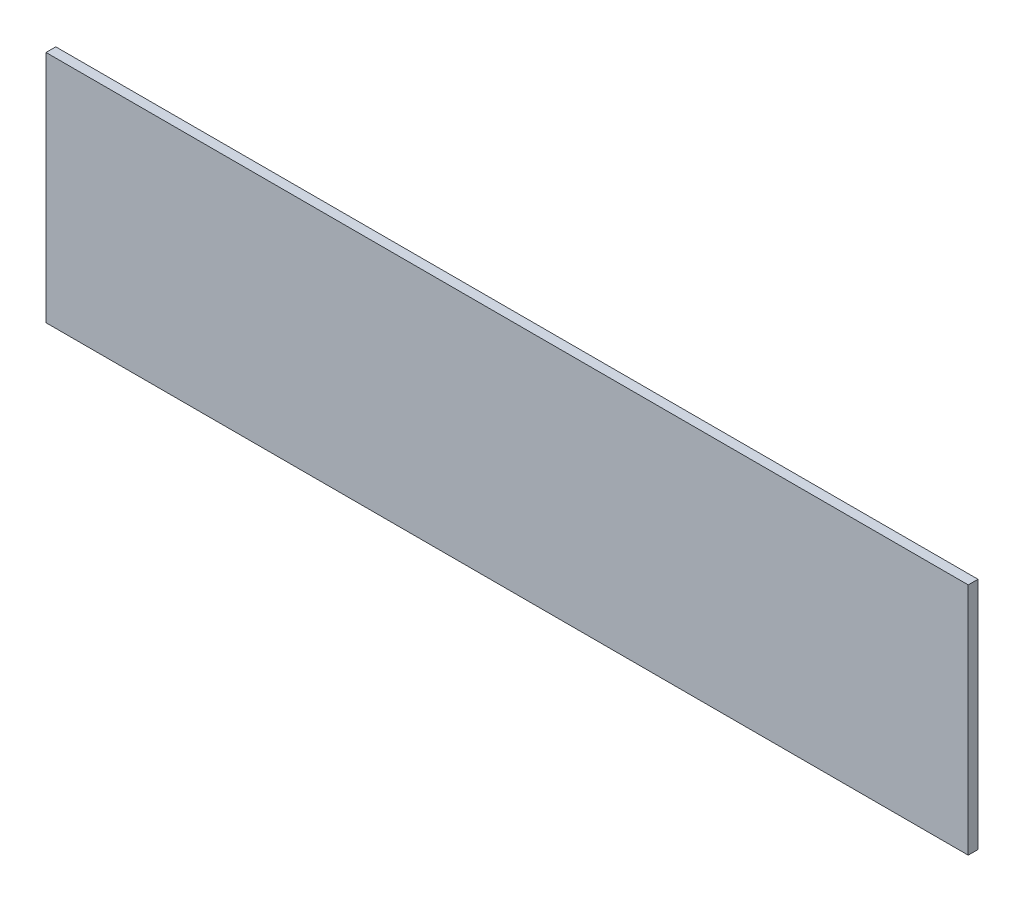
SolidWorks part; units mm, degrees
material "ABS"
ref_plane "X-Y Datum" through (0, 0, 0) normal (0, 0, 1) x (1, 0, 0)
ref_plane "X-Z Datum" through (0, 0, 0) normal (0, 1, 0) x (1, 0, 0)
ref_plane "Y-Z Datum" through (0, 0, 0) normal (1, 0, 0) x (0, 0, -1)
sketch "Sketch1" plane through (0, 0, 0) normal (0, 0, 1) x (1, 0, 0)
  line L1 (-149.85, 38.0375) -> (149.85, 38.0375)
  line L2 (-149.85, 38.0375) -> (-149.85, -38.0375)
  line L3 (-149.85, -38.0375) -> (149.85, -38.0375)
  line L4 (149.85, 38.0375) -> (149.85, -38.0375)
  line L5 (-149.85, 38.0375) -> (149.85, -38.0375) construction
  line L6 (-149.85, -38.0375) -> (149.85, 38.0375) construction
  point P0 (0, 0)
  dimension "D1" = 76.075
  dimension "D2" = 299.7
extrude "Boss-Extrude1" add sketch "Sketch1" along normal blind 3.175
